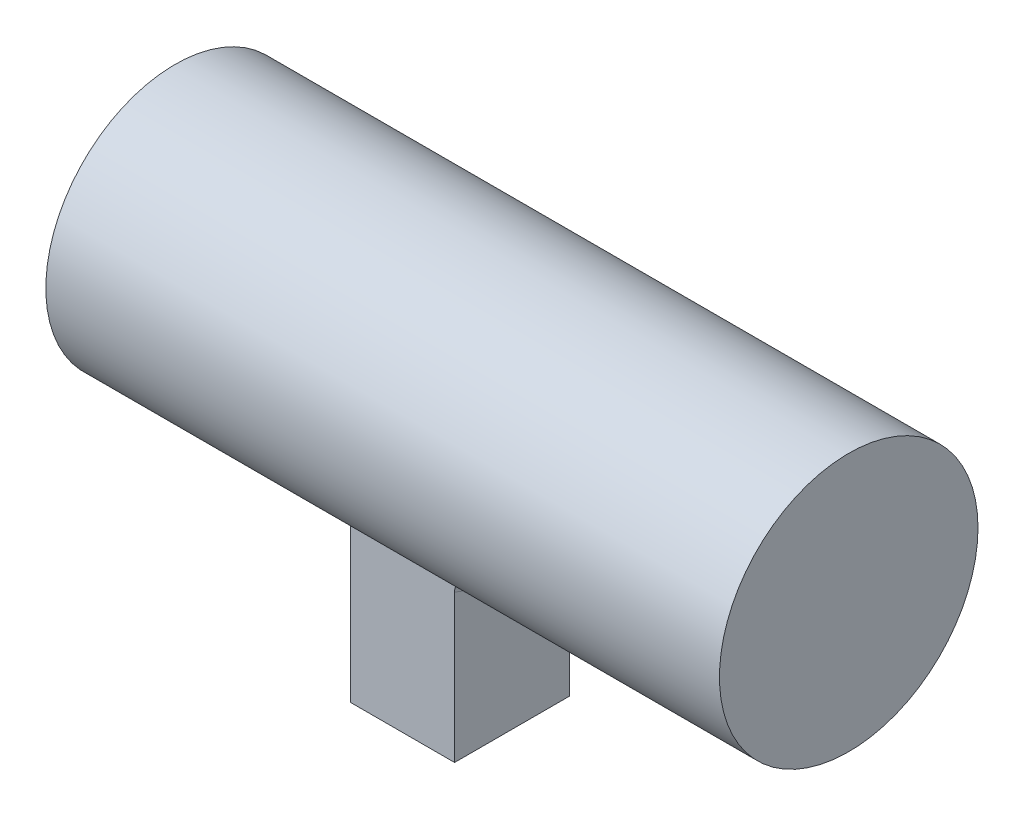
SolidWorks part; units mm, degrees
ref_plane "前视基准面" through (0, 0, 0) normal (0, 0, 1) x (1, 0, 0)
ref_plane "上视基准面" through (0, 0, 0) normal (0, 1, 0) x (1, 0, 0)
ref_plane "右视基准面" through (0, 0, 0) normal (1, 0, 0) x (0, 0, -1)
other "Configuration Table"
sketch "草图1" plane through (0, 0, 0) normal (0, 1, 0) x (1, 0, 0)
  line L1 (-7.7225, 8.5123) -> (7.7225, 8.5123)
  line L2 (-7.7225, 8.5123) -> (-7.7225, -8.5123)
  line L3 (-7.7225, -8.5123) -> (7.7225, -8.5123)
  line L4 (7.7225, 8.5123) -> (7.7225, -8.5123)
  line L5 (-7.7225, 8.5123) -> (7.7225, -8.5123) construction
  line L6 (-7.7225, -8.5123) -> (7.7225, 8.5123) construction
  point P0 (0, 0)
extrude "凸台-拉伸1" add sketch "草图1" along normal blind 50
sketch "草图2" plane through (7.7225, 0, 0) normal (1, 0, 0) x (0, 0, -1)
  circle A0 centre (0, 41.3121) radius 19.191
extrude "凸台-拉伸2" add sketch "草图2" against normal blind 50 and the other way blind 50
fillet "圆角3" radius 2 1 edges at (7.7225, 22.1211, 0)
